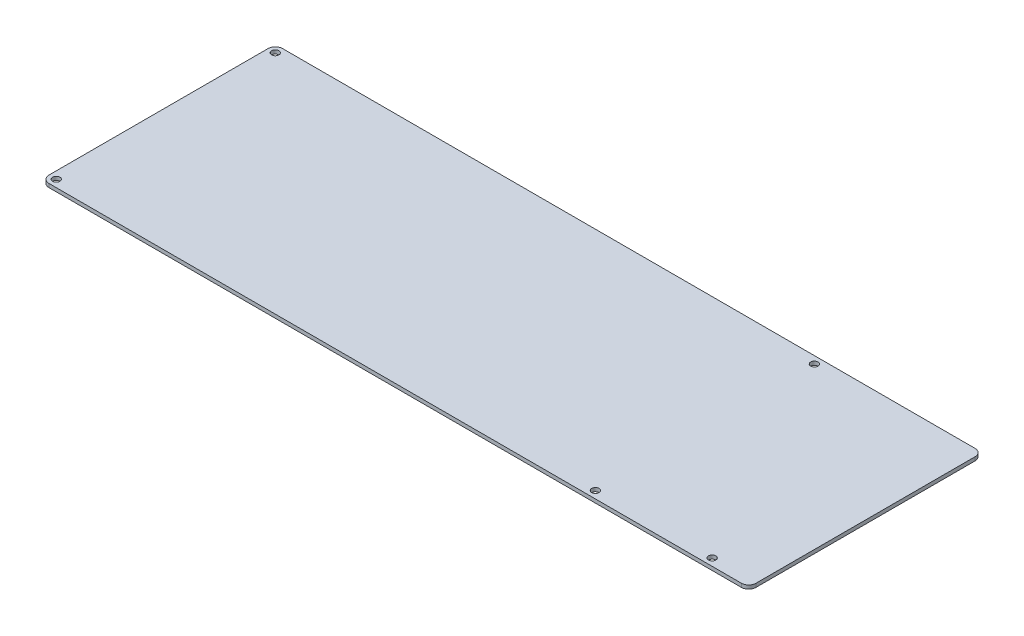
SolidWorks part; units mm, degrees
material "Delrin 2700 NC010, Low Viscosity Acetal Copolymer (SS)"
ref_plane "Front" through (0, 0, 0) normal (0, 0, 1) x (1, 0, 0)
ref_plane "Top" through (0, 0, 0) normal (0, 1, 0) x (1, 0, 0)
ref_plane "Right" through (0, 0, 0) normal (1, 0, 0) x (0, 0, -1)
sketch "Sketch1" plane through (0, 0, 0) normal (0, 1, 0) x (1, 0, 0)
  line L0 (-641.8801, 168.4566) -> (-641.8801, 78.4566) construction
  line L1 (-654.5801, 65.7566) -> (-39.6101, 65.7566)
  line L2 (-654.5801, 65.7566) -> (-654.5801, 268.9566)
  line L3 (-654.5801, 268.9566) -> (-39.6101, 268.9566)
  line L4 (-39.6101, 65.7566) -> (-39.6101, 268.9566)
  line L5 (-641.8801, 78.4566) -> (-541.8801, 78.4566) construction
  line L6 (-377.4301, 256.2566) -> (-192.0101, 256.2566) construction
  line L7 (-52.3101, 97.5066) -> (-52.3101, 237.2066) construction
  line L8 (-648.2301, 262.6066) -> (-45.9601, 262.6066) construction
  line L9 (-45.9601, 72.1066) -> (-45.9601, 262.6066) construction
  line L10 (-648.2301, 72.1066) -> (-45.9601, 72.1066) construction
  line L11 (-648.2301, 72.1066) -> (-648.2301, 262.6066) construction
  line L12 (-179.3101, 268.9566) -> (-179.3101, 65.7566) construction
  line L13 (-141.2101, 237.2066) -> (-141.2101, 97.5066) construction
  circle A0 centre (-648.2301, 262.6066) radius 3.175
  circle A1 centre (-648.2301, 72.1066) radius 3.175
  circle A2 centre (-45.9601, 262.6066) radius 3.175
  circle A3 centre (-45.9601, 72.1066) radius 3.175
  circle A4 centre (-179.3101, 72.1066) radius 3.175
  circle A5 centre (-179.3101, 262.6066) radius 3.175
  circle A6 centre (-77.7101, 72.1066) radius 3.175
  point P30 (0, 0)
  point P32 (-67.6912, 68.0344)
  dimension "D6" = 6.35
  dimension "D1" = 12.7
  dimension "D2" = 12.7
  dimension "D3" = 12.7
  dimension "D4" = 12.7
  dimension "D7" = 38.1
  dimension "D8" = 31.75
  dimension "D5" = 6.35
extrude "Boss-Extrude1" add sketch "Sketch1" against normal blind 3.175 contours A3 | L1 L4 L3 L2 A6 A5 A4 A3 A2 A1 A0 | A2 region at (-347.2486, 0, -167.3808) region at (-45.9601, 0, -262.6066) region at (-45.9601, 0, -72.1066)
fillet "Fillet1" radius 6.35 4 edges at (-39.6101, -1.5875, -268.9566) (-654.5801, -1.5875, -268.9566) (-39.6101, -1.5875, -65.7566) (-654.5801, -1.5875, -65.7566)
